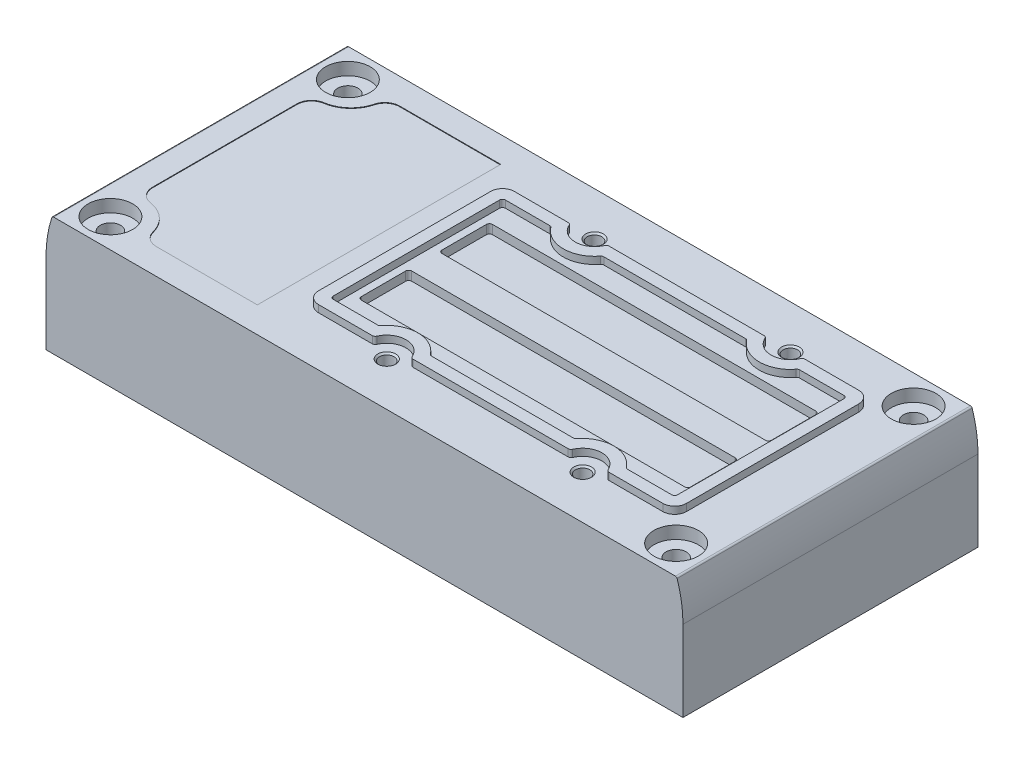
SolidWorks part; units mm, degrees
ref_plane "Front Plane" through (0, 0, 0) normal (0, 0, 1) x (1, 0, 0)
ref_plane "Top Plane" through (0, 0, 0) normal (0, 1, 0) x (1, 0, 0)
ref_plane "Right Plane" through (0, 0, 0) normal (1, 0, 0) x (0, 0, -1)
ref_plane "Plane1" through (0, 0, 0) normal (0, 0, 1) x (1, 0, 0)
sketch "Sketch1" plane through (0, 0, 0) normal (0, 0, 1) x (1, 0, 0)
  line L0 (-53.65, 13.6) -> (-53.65, 0)
  line L1 (-53.65, 0) -> (53.65, 0)
  line L2 (53.65, 0) -> (53.65, 13.6)
  line L3 (52.3818, 20) -> (-52.3818, 20)
  arc A0 (53.65, 13.6) -> (52.667, 19.7929) centre (33.65, 13.6) ccw
  arc A1 (52.667, 19.7929) -> (52.3818, 20) centre (52.3818, 19.7) ccw
  arc A2 (-52.3818, 20) -> (-52.667, 19.7929) centre (-52.3818, 19.7) ccw
  arc A3 (-52.667, 19.7929) -> (-53.65, 13.6) centre (-33.65, 13.6) ccw
extrude "Boss-Extrude1" add sketch "Sketch1" against normal blind 24.85 and the other way blind 24.85
ref_plane "Plane2" through (0, 0, 20) normal (0, 0, 1) x (1, 0, 0)
sketch "Sketch2" plane through (0, 0, 20) normal (0, 0, 1) x (1, 0, 0)
  line L0 (47.65, 20) -> (51.4, 20)
  line L1 (51.4, 20) -> (51.4, 17.9)
  line L2 (51.4, 17.9) -> (49.35, 17.9)
  line L3 (49.35, 17.9) -> (49.35, 12.7732)
  line L4 (49.35, 12.7732) -> (49.05, 12.6)
  line L5 (49.05, 12.6) -> (49.05, 12)
  line L6 (49.05, 12) -> (49.35, 12)
  line L7 (49.35, 12) -> (49.35, 0)
  line L8 (49.35, 0) -> (47.65, 0)
  line L9 (47.65, 0) -> (47.65, 20)
  line L10 (47.65, 0) -> (47.65, 20) construction
revolve "Cut-Revolve1" cut sketch "Sketch2" angle 360 about L10 reverse direction yes
ref_plane "Plane3" through (0, 0, -20) normal (0, 0, 1) x (1, 0, 0)
sketch "Sketch3" plane through (0, 0, -20) normal (0, 0, 1) x (1, 0, 0)
  line L0 (47.65, 20) -> (51.4, 20)
  line L1 (51.4, 20) -> (51.4, 17.9)
  line L2 (51.4, 17.9) -> (49.35, 17.9)
  line L3 (49.35, 17.9) -> (49.35, 12.7732)
  line L4 (49.35, 12.7732) -> (49.05, 12.6)
  line L5 (49.05, 12.6) -> (49.05, 12)
  line L6 (49.05, 12) -> (49.35, 12)
  line L7 (49.35, 12) -> (49.35, 0)
  line L8 (49.35, 0) -> (47.65, 0)
  line L9 (47.65, 0) -> (47.65, 20)
  line L10 (47.65, 0) -> (47.65, 20) construction
revolve "Cut-Revolve2" cut sketch "Sketch3" angle 360 about L10 reverse direction yes
ref_plane "Plane4" through (0, 0, -20) normal (0, 0, 1) x (1, 0, 0)
sketch "Sketch4" plane through (0, 0, -20) normal (0, 0, 1) x (1, 0, 0)
  line L0 (-47.65, 20) -> (-43.9, 20)
  line L1 (-43.9, 20) -> (-43.9, 17.9)
  line L2 (-43.9, 17.9) -> (-45.95, 17.9)
  line L3 (-45.95, 17.9) -> (-45.95, 12.7732)
  line L4 (-45.95, 12.7732) -> (-46.25, 12.6)
  line L5 (-46.25, 12.6) -> (-46.25, 12)
  line L6 (-46.25, 12) -> (-45.95, 12)
  line L7 (-45.95, 12) -> (-45.95, 0)
  line L8 (-45.95, 0) -> (-47.65, 0)
  line L9 (-47.65, 0) -> (-47.65, 20)
  line L10 (-47.65, 0) -> (-47.65, 20) construction
revolve "Cut-Revolve3" cut sketch "Sketch4" angle 360 about L10 reverse direction yes
ref_plane "Plane5" through (0, 0, 20) normal (0, 0, 1) x (1, 0, 0)
sketch "Sketch5" plane through (0, 0, 20) normal (0, 0, 1) x (1, 0, 0)
  line L0 (-47.65, 20) -> (-43.9, 20)
  line L1 (-43.9, 20) -> (-43.9, 17.9)
  line L2 (-43.9, 17.9) -> (-45.95, 17.9)
  line L3 (-45.95, 17.9) -> (-45.95, 12.7732)
  line L4 (-45.95, 12.7732) -> (-46.25, 12.6)
  line L5 (-46.25, 12.6) -> (-46.25, 12)
  line L6 (-46.25, 12) -> (-45.95, 12)
  line L7 (-45.95, 12) -> (-45.95, 0)
  line L8 (-45.95, 0) -> (-47.65, 0)
  line L9 (-47.65, 0) -> (-47.65, 20)
  line L10 (-47.65, 0) -> (-47.65, 20) construction
revolve "Cut-Revolve4" cut sketch "Sketch5" angle 360 about L10 reverse direction yes
ref_plane "Plane6" through (0, 20, 0) normal (0, 1, 0) x (1, 0, 0)
sketch "Sketch6" plane through (0, 20, 0) normal (0, 1, 0) x (1, 0, 0)
  line L0 (-14.85, 10.52) -> (-14.85, 3.05)
  line L1 (-14.35, 2.55) -> (40.15, 2.55)
  line L2 (40.65, 3.05) -> (40.65, 10.55)
  line L3 (40.15, 11.05) -> (-14.32, 11.05)
  arc A0 (-14.85, 3.05) -> (-14.35, 2.55) centre (-14.35, 3.05) ccw
  arc A1 (40.15, 2.55) -> (40.65, 3.05) centre (40.15, 3.05) ccw
  arc A2 (40.65, 10.55) -> (40.15, 11.05) centre (40.15, 10.55) ccw
  arc A3 (-14.32, 11.05) -> (-14.85, 10.52) centre (-14.32, 10.52) ccw
extrude "Cut-Extrude1" cut sketch "Sketch6" against normal blind 1.5
ref_plane "Plane7" through (0, 20, 0) normal (0, 1, 0) x (1, 0, 0)
sketch "Sketch7" plane through (0, 20, 0) normal (0, 1, 0) x (1, 0, 0)
  line L0 (-14.32, -11.05) -> (40.15, -11.05)
  line L1 (40.65, -10.55) -> (40.65, -3.05)
  line L2 (40.15, -2.55) -> (-14.35, -2.55)
  line L3 (-14.85, -3.05) -> (-14.85, -10.52)
  arc A0 (-14.85, -10.52) -> (-14.32, -11.05) centre (-14.32, -10.52) ccw
  arc A1 (40.15, -11.05) -> (40.65, -10.55) centre (40.15, -10.55) ccw
  arc A2 (40.65, -3.05) -> (40.15, -2.55) centre (40.15, -3.05) ccw
  arc A3 (-14.35, -2.55) -> (-14.85, -3.05) centre (-14.35, -3.05) ccw
extrude "Cut-Extrude2" cut sketch "Sketch7" against normal blind 1.5
ref_plane "Plane8" through (0, 20, 0) normal (0, 1, 0) x (1, 0, 0)
sketch "Sketch8" plane through (0, 20, 0) normal (0, 1, 0) x (1, 0, 0)
  line L0 (-18.1, 14.5) -> (-18.1, -14.5)
  line L1 (-16.1, -16.5) -> (-7.0369, -16.5)
  line L2 (-0.1631, -16.5) -> (25.9631, -16.5)
  line L3 (32.8369, -16.5) -> (41.9, -16.5)
  line L4 (43.9, -14.5) -> (43.9, 14.5)
  line L5 (41.9, 16.5) -> (32.8369, 16.5)
  line L6 (25.9631, 16.5) -> (-0.1631, 16.5)
  line L7 (-7.0369, 16.5) -> (-16.1, 16.5)
  line L8 (-16.1, 14) -> (-16.1, -14)
  line L9 (-15.6, -14.5) -> (-8.1621, -14.5)
  line L10 (0.9621, -14.5) -> (24.8379, -14.5)
  line L11 (33.9621, -14.5) -> (41.4, -14.5)
  line L12 (41.9, -14) -> (41.9, 14)
  line L13 (41.4, 14.5) -> (33.9621, 14.5)
  line L14 (24.8379, 14.5) -> (0.9621, 14.5)
  line L15 (-8.1621, 14.5) -> (-15.6, 14.5)
  arc A0 (-18.1, -14.5) -> (-16.1, -16.5) centre (-16.1, -14.5) ccw
  arc A1 (-7.0369, -16.5) -> (-6.5787, -16.2) centre (-7.0369, -16) ccw
  arc A2 (-6.5787, -16.2) -> (-0.6213, -16.2) centre (-3.6, -17.5) cw
  arc A3 (-0.6213, -16.2) -> (-0.1631, -16.5) centre (-0.1631, -16) ccw
  arc A4 (25.9631, -16.5) -> (26.4213, -16.2) centre (25.9631, -16) ccw
  arc A5 (26.4213, -16.2) -> (32.3787, -16.2) centre (29.4, -17.5) cw
  arc A6 (32.3787, -16.2) -> (32.8369, -16.5) centre (32.8369, -16) ccw
  arc A7 (41.9, -16.5) -> (43.9, -14.5) centre (41.9, -14.5) ccw
  arc A8 (43.9, 14.5) -> (41.9, 16.5) centre (41.9, 14.5) ccw
  arc A9 (32.8369, 16.5) -> (32.3787, 16.2) centre (32.8369, 16) ccw
  arc A10 (32.3787, 16.2) -> (26.4213, 16.2) centre (29.4, 17.5) cw
  arc A11 (26.4213, 16.2) -> (25.9631, 16.5) centre (25.9631, 16) ccw
  arc A12 (-0.1631, 16.5) -> (-0.6213, 16.2) centre (-0.1631, 16) ccw
  arc A13 (-0.6213, 16.2) -> (-6.5787, 16.2) centre (-3.6, 17.5) cw
  arc A14 (-6.5787, 16.2) -> (-7.0369, 16.5) centre (-7.0369, 16) ccw
  arc A15 (-16.1, 16.5) -> (-18.1, 14.5) centre (-16.1, 14.5) ccw
  arc A16 (-16.1, -14) -> (-15.6, -14.5) centre (-15.6, -14) ccw
  arc A17 (-8.1621, -14.5) -> (-7.7654, -14.3043) centre (-8.1621, -14) ccw
  arc A18 (-7.7654, -14.3043) -> (0.5654, -14.3043) centre (-3.6, -17.5) cw
  arc A19 (0.5654, -14.3043) -> (0.9621, -14.5) centre (0.9621, -14) ccw
  arc A20 (24.8379, -14.5) -> (25.2346, -14.3043) centre (24.8379, -14) ccw
  arc A21 (25.2346, -14.3043) -> (33.5654, -14.3043) centre (29.4, -17.5) cw
  arc A22 (33.5654, -14.3043) -> (33.9621, -14.5) centre (33.9621, -14) ccw
  arc A23 (41.4, -14.5) -> (41.9, -14) centre (41.4, -14) ccw
  arc A24 (41.9, 14) -> (41.4, 14.5) centre (41.4, 14) ccw
  arc A25 (33.9621, 14.5) -> (33.5654, 14.3043) centre (33.9621, 14) ccw
  arc A26 (33.5654, 14.3043) -> (25.2346, 14.3043) centre (29.4, 17.5) cw
  arc A27 (25.2346, 14.3043) -> (24.8379, 14.5) centre (24.8379, 14) ccw
  arc A28 (0.9621, 14.5) -> (0.5654, 14.3043) centre (0.9621, 14) ccw
  arc A29 (0.5654, 14.3043) -> (-7.7654, 14.3043) centre (-3.6, 17.5) cw
  arc A30 (-7.7654, 14.3043) -> (-8.1621, 14.5) centre (-8.1621, 14) ccw
  arc A31 (-15.6, 14.5) -> (-16.1, 14) centre (-15.6, 14) ccw
extrude "Boss-Extrude2" add sketch "Sketch8" along normal blind 1.2
ref_plane "Plane9" through (0, 20, 0) normal (0, 1, 0) x (1, 0, 0)
sketch "Sketch9" plane through (0, 20, 0) normal (0, 1, 0) x (1, 0, 0)
  line L0 (-48.4, 12.1512) -> (-48.4, -12.1512)
  line L1 (-39.4234, -20.5) -> (-22.4, -20.5)
  line L2 (-22.4, -20.5) -> (-22.4, 20.5)
  line L3 (-22.4, 20.5) -> (-39.4234, 20.5)
  arc A0 (-48.4, -12.1512) -> (-46.2863, -14.6126) centre (-45.91, -12.1512) ccw
  arc A1 (-46.2863, -14.6126) -> (-41.8339, -18.6341) centre (-47.11, -20) cw
  arc A2 (-41.8339, -18.6341) -> (-39.4234, -20.5) centre (-39.4234, -18.01) ccw
  arc A3 (-39.4234, 20.5) -> (-41.8339, 18.6341) centre (-39.4234, 18.01) ccw
  arc A4 (-41.8339, 18.6341) -> (-46.2863, 14.6126) centre (-47.11, 20) cw
  arc A5 (-46.2863, 14.6126) -> (-48.4, 12.1512) centre (-45.91, 12.1512) ccw
extrude "Cut-Extrude3" cut sketch "Sketch9" against normal blind 0.1 and the other way blind 0.1
ref_plane "Plane10" through (0, 0, 0) normal (0, 1, 0) x (1, 0, 0)
sketch "Sketch10" plane through (0, 0, 0) normal (0, 1, 0) x (1, 0, 0)
  line L0 (-48.4, 12.1512) -> (-48.4, -12.1512)
  line L1 (-39.4234, -20.5) -> (-22.4, -20.5)
  line L2 (-22.4, -20.5) -> (-22.4, 20.5)
  line L3 (-22.4, 20.5) -> (-39.4234, 20.5)
  arc A0 (-48.4, -12.1512) -> (-46.2863, -14.6126) centre (-45.91, -12.1512) ccw
  arc A1 (-46.2863, -14.6126) -> (-41.8339, -18.6341) centre (-47.11, -20) cw
  arc A2 (-41.8339, -18.6341) -> (-39.4234, -20.5) centre (-39.4234, -18.01) ccw
  arc A3 (-39.4234, 20.5) -> (-41.8339, 18.6341) centre (-39.4234, 18.01) ccw
  arc A4 (-41.8339, 18.6341) -> (-46.2863, 14.6126) centre (-47.11, 20) cw
  arc A5 (-46.2863, 14.6126) -> (-48.4, 12.1512) centre (-45.91, 12.1512) ccw
extrude "Cut-Extrude4" cut sketch "Sketch10" along normal blind 19
ref_plane "Plane11" through (0, 0, 0) normal (0, 1, 0) x (1, 0, 0)
sketch "Sketch11" plane through (0, 0, 0) normal (0, 1, 0) x (1, 0, 0)
  line L0 (-22.4, -20.5) -> (40.208, -20.5)
  line L1 (48.4, -12.0497) -> (48.4, 12.0497)
  line L2 (40.208, 20.5) -> (-22.4, 20.5)
  line L3 (-22.4, 20.5) -> (-22.4, -20.5)
  arc A0 (40.208, -20.5) -> (42.0607, -18.9391) centre (40.208, -18.62) ccw
  arc A1 (42.0607, -18.9391) -> (46.9131, -13.8882) centre (48.22, -20) cw
  arc A2 (46.9131, -13.8882) -> (48.4, -12.0497) centre (46.52, -12.0497) ccw
  arc A3 (48.4, 12.0497) -> (46.9131, 13.8882) centre (46.52, 12.0497) ccw
  arc A4 (46.9131, 13.8882) -> (42.0607, 18.9391) centre (48.22, 20) cw
  arc A5 (42.0607, 18.9391) -> (40.208, 20.5) centre (40.208, 18.62) ccw
extrude "Cut-Extrude5" cut sketch "Sketch11" along normal blind 10
ref_plane "Plane12" through (0, 0, -17.5) normal (0, 0, 1) x (1, 0, 0)
sketch "Sketch12" plane through (0, 0, -17.5) normal (0, 0, 1) x (1, 0, 0)
  line L0 (-3.6, 20) -> (-2.1, 20)
  line L1 (-2.1, 20) -> (-2.3705, 19.7295)
  line L2 (-2.3705, 19.7295) -> (-2.3705, 13.4)
  line L3 (-2.3705, 13.4) -> (-3.6, 13.4)
  line L4 (-3.6, 13.4) -> (-3.6, 20)
  line L5 (-3.6, 13.4) -> (-3.6, 20) construction
revolve "Cut-Revolve5" cut sketch "Sketch12" angle 360 about L5 reverse direction yes
cosmetic thread "Cosmetic Thread1" parameters "D1"=6.6, "D2"=3
ref_plane "Plane13" through (0, 0, 17.5) normal (0, 0, 1) x (1, 0, 0)
sketch "Sketch13" plane through (0, 0, 17.5) normal (0, 0, 1) x (1, 0, 0)
  line L0 (-3.6, 20) -> (-2.1, 20)
  line L1 (-2.1, 20) -> (-2.3705, 19.7295)
  line L2 (-2.3705, 19.7295) -> (-2.3705, 13.4)
  line L3 (-2.3705, 13.4) -> (-3.6, 13.4)
  line L4 (-3.6, 13.4) -> (-3.6, 20)
  line L5 (-3.6, 13.4) -> (-3.6, 20) construction
revolve "Cut-Revolve6" cut sketch "Sketch13" angle 360 about L5 reverse direction yes
cosmetic thread "Cosmetic Thread2" parameters "D1"=6.6, "D2"=3
ref_plane "Plane14" through (0, 0, 17.5) normal (0, 0, 1) x (1, 0, 0)
sketch "Sketch14" plane through (0, 0, 17.5) normal (0, 0, 1) x (1, 0, 0)
  line L0 (29.4, 20) -> (30.9, 20)
  line L1 (30.9, 20) -> (30.6295, 19.7295)
  line L2 (30.6295, 19.7295) -> (30.6295, 13.4)
  line L3 (30.6295, 13.4) -> (29.4, 13.4)
  line L4 (29.4, 13.4) -> (29.4, 20)
  line L5 (29.4, 13.4) -> (29.4, 20) construction
revolve "Cut-Revolve7" cut sketch "Sketch14" angle 360 about L5 reverse direction yes
cosmetic thread "Cosmetic Thread3" parameters "D1"=6.6, "D2"=3
ref_plane "Plane15" through (0, 0, -17.5) normal (0, 0, 1) x (1, 0, 0)
sketch "Sketch15" plane through (0, 0, -17.5) normal (0, 0, 1) x (1, 0, 0)
  line L0 (29.4, 20) -> (30.9, 20)
  line L1 (30.9, 20) -> (30.6295, 19.7295)
  line L2 (30.6295, 19.7295) -> (30.6295, 13.4)
  line L3 (30.6295, 13.4) -> (29.4, 13.4)
  line L4 (29.4, 13.4) -> (29.4, 20)
  line L5 (29.4, 13.4) -> (29.4, 20) construction
revolve "Cut-Revolve8" cut sketch "Sketch15" angle 360 about L5 reverse direction yes
cosmetic thread "Cosmetic Thread4" parameters "D1"=6.6, "D2"=3
